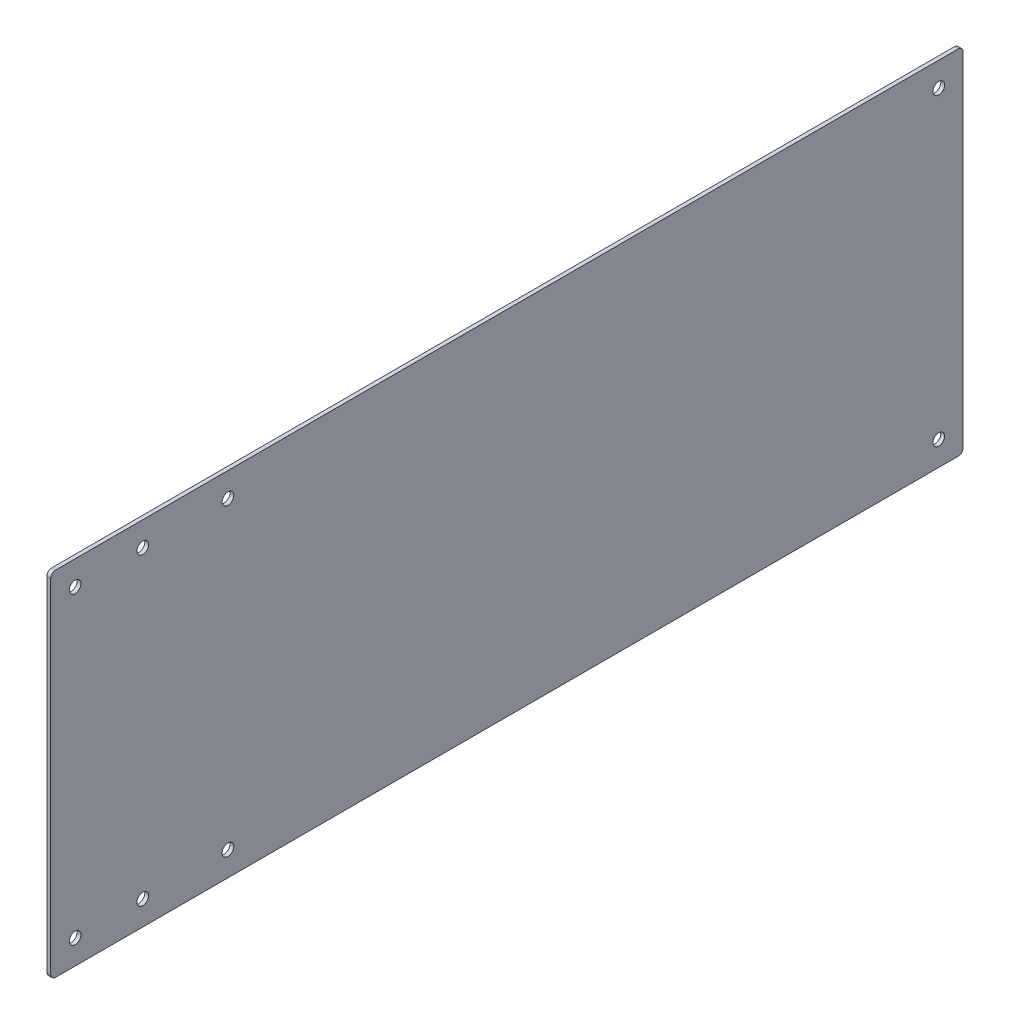
SolidWorks part; units mm, degrees
material "6061 Alloy"
ref_plane "Front Plane" through (0, 0, 0) normal (0, 0, 1) x (1, 0, 0)
ref_plane "Top Plane" through (0, 0, 0) normal (0, 1, 0) x (1, 0, 0)
ref_plane "Right Plane" through (0, 0, 0) normal (1, 0, 0) x (0, 0, -1)
sketch "Sketch1" plane through (0, 0, 0) normal (1, 0, 0) x (0, 0, -1)
  line L0 (0, 55) -> (0, -55) construction
  line L1 (-187.5, -72.49) -> (187.5, -72.49)
  line L2 (-187.5, -72.49) -> (-187.5, 72.49)
  line L3 (-187.5, 72.49) -> (187.5, 72.49)
  line L4 (187.5, -72.49) -> (187.5, 72.49)
  line L5 (-187.5, -72.49) -> (187.5, 72.49) construction
  line L6 (-187.5, 72.49) -> (187.5, -72.49) construction
  line L7 (55, 0) -> (-55, 0) construction
  point P0 (0, 0)
  point P6 (-172.5, 65)
  point P9 (172.5, 65)
  point P12 (-172.5, -65)
  point P13 (172.5, -65)
  dimension "D1" = 375
  dimension "D2" = 144.98
  dimension "D3" = 7.49
  dimension "D4" = 15
base flange "Base-Flange1" sketch "Sketch1" thickness 1.5875 reverse thickness direction no parameters "D1"=0.7366
hole_wizard "M4 Clearance Hole1" positions "Sketch6" profile "Sketch8" hole size "M4" standard "ANSI Metric" end condition up to next
sketch "Sketch6" plane through (-1.5875, 0, 0) normal (-1, 0, 0) x (0, 0, 1)
  line L0 (-187.5, 72.49) -> (187.5, 72.49) construction
  line L1 (187.5, 72.49) -> (187.5, -72.49) construction
  point P0 (177.5, 62.49)
  dimension "D1" = 10
  dimension "D2" = 10
sketch "Sketch8" plane through (-1.5875, 62.49, 177.5) normal (0, 1, 0) x (0, 0, 1)
  line L0 (0, 0) -> (0, 1.5875)
  line L1 (0, 1.5875) -> (2.4, 1.5875)
  line L2 (2.4, 1.5875) -> (2.4, 0)
  line L5 (2.4, 0) -> (0, 0)
  line L11 (0, -6.35) -> (0, 107.95) construction
  dimension "Thru Hole Dia." = 4.8
  dimension "Thru Hole Depth" = 1.5875
mirror "Mirror1" about plane through (0, 0, 0) normal (0, 0, 1) of "M4 Clearance Hole1"
mirror "Mirror2" about plane through (0, 0, 0) normal (0, 1, 0) of "Mirror1", "M4 Clearance Hole1"
sketch "Sketch9" plane through (0, 0, 0) normal (1, 0, 0) x (0, 0, -1)
  line L0 (187.5, 72.49) -> (-187.5, 72.49) construction
  line L1 (-187.5, 72.49) -> (-187.5, -72.49) construction
  point P0 (-149.66, 62.49)
  point P1 (-114.66, 62.49)
  dimension "D1" = 10
  dimension "D2" = 10
  dimension "D3" = 35
  dimension "D4" = 37.84
hole_wizard "M4 Clearance Hole2" positions "3DSketch1" profile "Sketch10" hole size "M4" standard "ANSI Metric" end condition through all
sketch3d "3DSketch1"
  point P0 (0, 62.49, 149.66)
  point P3 (0, 62.49, 114.66)
sketch "Sketch10" plane through (0, 62.49, 149.66) normal (0, 1, 0) x (0, 0, -1)
  line L0 (0, 0) -> (0, 1.5875)
  line L1 (0, 1.5875) -> (2.4, 1.5875)
  line L2 (2.4, 1.5875) -> (2.4, 0)
  line L5 (2.4, 0) -> (0, 0)
  line L11 (0, -6.35) -> (0, 107.95) construction
  dimension "Thru Hole Dia." = 4.8
  dimension "Thru Hole Depth" = 1.5875
mirror "Mirror3" about plane through (0, 0, 0) normal (0, 1, 0) of "M4 Clearance Hole2"
fillet "Fillet1" radius 2 1 edges at (-0.7937, 72.49, 187.5)
fillet "Fillet2" radius 2 1 edges at (-0.7937, -72.49, 187.5)
fillet "Fillet3" radius 2 1 edges at (-0.7937, 72.49, -187.5)
fillet "Fillet4" radius 2 1 edges at (-0.7937, -72.49, -187.5)
sketch "Lignes de pliage1" [suppressed] plane through (0, 0, 0) normal (0, 1, 0) x (1, 0, 0)
sketch "Cube de visualisation1" [suppressed] plane through (0, 0, 0) normal (0, 1, 0) x (1, 0, 0)
sheet metal parameters "Tôlerie1" thickness 1.5875 parameters "D1"=0.7366
flat pattern "Etat déplié1" [suppressed]
sketch "Lignes de pliage2" plane through (0, 0, 0) normal (0, 1, 0) x (1, 0, 0)
sketch3d "Cube de visualisation2" [suppressed]
  line L0 (-187.5, -72.49, 0) -> (187.5, -72.49, 0) construction
  line L1 (-187.5, 72.49, 0) -> (187.5, 72.49, 0) construction
  line L2 (-187.5, -72.49, 0) -> (-187.5, 72.49, 0) construction
  line L3 (187.5, -72.49, 0) -> (187.5, 72.49, 0) construction
sheet metal parameters "Tôlerie2" thickness 1.5875 parameters "D1"=0.7366
flat pattern "Etat déplié1"
sketch "Lignes de pliage2" plane through (0, 0, 0) normal (0, 1, 0) x (1, 0, 0)
sketch3d "Cube de visualisation2" [suppressed]
  line L0 (187.5, -72.49, 0) -> (-187.5, -72.49, 0) construction
  line L1 (187.5, 72.49, 0) -> (-187.5, 72.49, 0) construction
  line L2 (187.5, -72.49, 0) -> (187.5, 72.49, 0) construction
  line L3 (-187.5, -72.49, 0) -> (-187.5, 72.49, 0) construction
sheet metal parameters "Tôlerie3" thickness 1.5875 parameters "D1"=0.7366
flat pattern "Etat déplié1"
sketch "Lignes de pliage2" plane through (0, 0, 0) normal (0, 1, 0) x (1, 0, 0)
sketch3d "Cube de visualisation2" [suppressed]
  line L0 (187.5, -72.49, 0) -> (-187.5, -72.49, 0) construction
  line L1 (187.5, 72.49, 0) -> (-187.5, 72.49, 0) construction
  line L2 (187.5, -72.49, 0) -> (187.5, 72.49, 0) construction
  line L3 (-187.5, -72.49, 0) -> (-187.5, 72.49, 0) construction
sheet metal parameters "Tôlerie4" thickness 1.5875 parameters "D1"=0.7366
flat pattern "Etat déplié1"
sketch "Lignes de pliage2" plane through (0, 0, 0) normal (0, 1, 0) x (1, 0, 0)
sketch3d "Cube de visualisation2" [suppressed]
  line L0 (187.5, -72.49, 0) -> (-187.5, -72.49, 0) construction
  line L1 (187.5, 72.49, 0) -> (-187.5, 72.49, 0) construction
  line L2 (187.5, -72.49, 0) -> (187.5, 72.49, 0) construction
  line L3 (-187.5, -72.49, 0) -> (-187.5, 72.49, 0) construction
sheet metal parameters "Tôlerie5" thickness 1.5875 parameters "D1"=0.7366
flat pattern "Etat déplié1"
sketch "Lignes de pliage2" plane through (0, 0, 0) normal (0, 1, 0) x (1, 0, 0)
sketch3d "Cube de visualisation2" [suppressed]
  line L0 (187.5, -72.49, 0) -> (-187.5, -72.49, 0) construction
  line L1 (187.5, 72.49, 0) -> (-187.5, 72.49, 0) construction
  line L2 (187.5, -72.49, 0) -> (187.5, 72.49, 0) construction
  line L3 (-187.5, -72.49, 0) -> (-187.5, 72.49, 0) construction
sheet metal parameters "Tôlerie6" thickness 1.5875 parameters "D1"=0.7366
flat pattern "Etat déplié1"
sketch "Lignes de pliage2" plane through (0, 0, 0) normal (0, 1, 0) x (1, 0, 0)
sketch3d "Cube de visualisation2" [suppressed]
  line L0 (187.5, -72.49, 0) -> (-187.5, -72.49, 0) construction
  line L1 (187.5, 72.49, 0) -> (-187.5, 72.49, 0) construction
  line L2 (187.5, -72.49, 0) -> (187.5, 72.49, 0) construction
  line L3 (-187.5, -72.49, 0) -> (-187.5, 72.49, 0) construction
